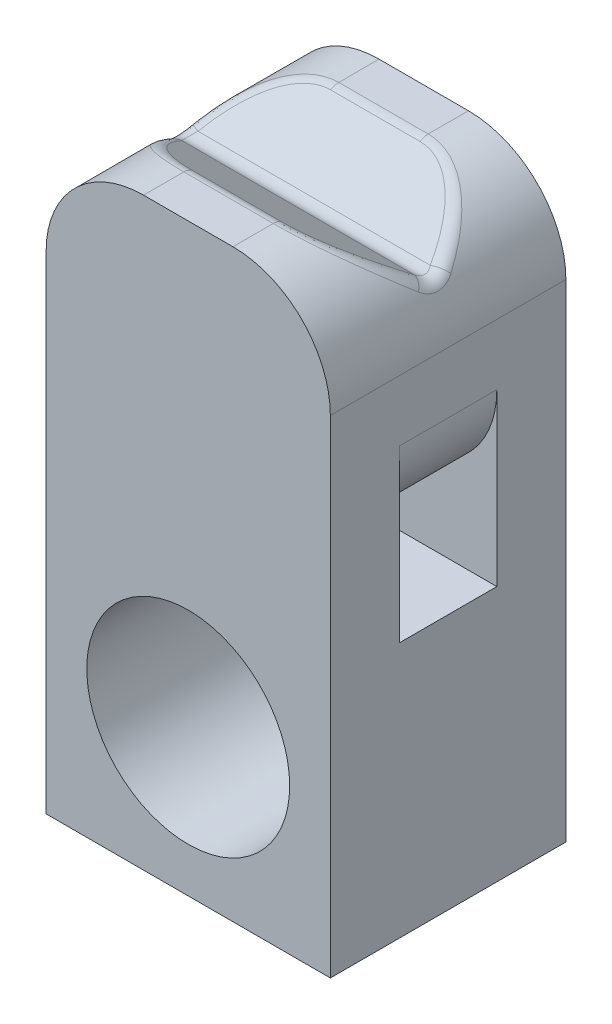
SolidWorks part; units mm, degrees
ref_plane "Front Plane" through (0, 0, 0) normal (0, 0, 1) x (1, 0, 0)
ref_plane "Top Plane" through (0, 0, 0) normal (0, 1, 0) x (1, 0, 0)
ref_plane "Right Plane" through (0, 0, 0) normal (1, 0, 0) x (0, 0, -1)
sketch "Sketch2" plane through (0, 0, 0) normal (0, 1, 0) x (1, 0, 0)
  line L0 (-2.9175, -2.4175) -> (2.9175, -2.4175) construction
  line L1 (-2.9175, -2.4175) -> (-2.9175, 2.4175)
  line L2 (2.9175, -2.4175) -> (2.9175, 2.4175) construction
  line L3 (-2.9175, 2.4175) -> (2.9175, 2.4175) construction
  line L4 (-2.9175, -2.4175) -> (2.9175, 2.4175) construction
  line L5 (2.9175, -2.4175) -> (-2.9175, 2.4175) construction
  line L6 (-2.9175, 2.4175) -> (2.9175, 2.4175)
  line L7 (-2.9175, -2.4175) -> (2.9175, -2.4175)
  line L8 (2.9175, -2.4175) -> (2.9175, 2.4175)
  point P1 (0, 0)
  dimension "D3" = 4.835
  dimension "D4" = 5.835
extrude "Boss-Extrude1" add sketch "Sketch2" along normal blind 10
sketch "Sketch3" plane through (0, 10, 0) normal (0, 1, 0) x (1, 0, 0)
  line L4 (2.9175, -2.4175) -> (2.9175, 2.4175)
  line L5 (2.9175, 2.4175) -> (-2.9175, 2.4175)
  line L6 (-2.9175, 2.4175) -> (-2.9175, -2.4175)
  line L7 (-2.9175, -2.4175) -> (2.9175, -2.4175)
  line L8 (2.9175, -2.4175) -> (2.9175, 2.4175)
  line L9 (2.9175, 2.4175) -> (-2.9175, 2.4175)
  line L10 (-2.9175, 2.4175) -> (-2.9175, -2.4175)
  line L11 (-2.9175, -2.4175) -> (2.9175, -2.4175)
  dimension "D1" = 0
extrude "Boss-Extrude2" add sketch "Sketch3" along normal blind 2
sketch "Sketch4" plane through (2.9175, 0, 0) normal (1, 0, 0) x (0, 0, -1)
  line L0 (0, 0) -> (0, 12) construction
  line L1 (-2.4175, 12) -> (2.4175, 12) construction
  line L3 (-1, 5.25) -> (1, 5.25)
  line L4 (-1, 5.25) -> (-1, 6.75)
  line L5 (-1, 6.75) -> (1, 6.75)
  line L6 (1, 5.25) -> (1, 6.75)
  line L7 (-1, 5.25) -> (1, 6.75) construction
  line L8 (-1, 6.75) -> (1, 5.25) construction
  point P5 (0, 6)
  dimension "D1" = 1.5
  dimension "D2" = 2
extrude "Cut-Extrude1" cut sketch "Sketch4" against normal up to surface (5.835 mm away) up to face at (-2.9175, 6, 0)
fillet "Fillet1" radius 2 4 edges at (2.9175, 12, 0) (-2.9175, 12, 0) (-2.9175, 6.75, 0) (2.9175, 6.75, 0)
sketch "Sketch6" plane through (0, 0, 0) normal (0, 0, 1) x (1, 0, 0)
  line L0 (0, 0) -> (0, 3) construction
  circle A0 centre (0, 3) radius 2.0825
  dimension "D2" = 4.165
  dimension "D1" = 3
extrude "Cut-Extrude2" cut sketch "Sketch6" against normal through all both and the other way through all
sketch "Sketch7" plane through (-2.9175, 0, 0) normal (-1, 0, 0) x (0, 0, 1)
  line L0 (-1.5, 12) -> (1.5, 12)
  line L1 (1.5, 12) -> (0, 11)
  line L2 (0, 11) -> (-1.5, 12)
  line L3 (0, 11) -> (0, 12) construction
  line L5 (-2.4175, 12) -> (2.4175, 12) construction
  point P4 (0, 0)
  point P7 (-1.9101, 11.9983)
  point P8 (0, 0)
  point P9 (0, 11.9983)
  point P10 (0, 12)
  point P12 (0, 0)
  dimension "D1" = 1
  dimension "D2" = 3
extrude "Cut-Extrude3" cut sketch "Sketch7" against normal up to surface (5.5671 mm away) up to face at (2.1246, 11.2071, 0)
fillet "Fillet2" radius 0.3 7 edges at (0, 11, 0) (1.9175, 11.7321, -1.0981) (1.9175, 11.7321, 1.0981) (-1.9175, 11.7321, 1.0981) (-1.9175, 11.7321, -1.0981) (0, 12, 1.5) (0, 12, -1.5)
equation "\"chuck_width\"=5"
equation "\"D3@Sketch2\"=\"chuck_width\"-\"tol\"/2"
equation "\"chuck_length\" = 6"
equation "\"D4@Sketch2\"=\"chuck_length\"-\"tol\"/2"
equation "\"chuck_angle\"=0"
equation "\"D2@Sketch2\"=\"chuck_angle\""
equation "\"D1@Sketch2\"=\"chuck_angle\""
equation "\"chuck_depth\"= 10"
equation "\"chuck_height\"= 2"
equation "\"pin_offset\"=3"
equation "\"D1@Sketch6\"=\"pin_offset\""
equation "\"pin_dia\"= 4"
equation "\"D2@Sketch6\"=\"pin_dia\"+\"tol\"/2"
equation "\"tol\"= 0.33"
equation "\"D1@Boss-Extrude1\"=\"chuck_depth\""
